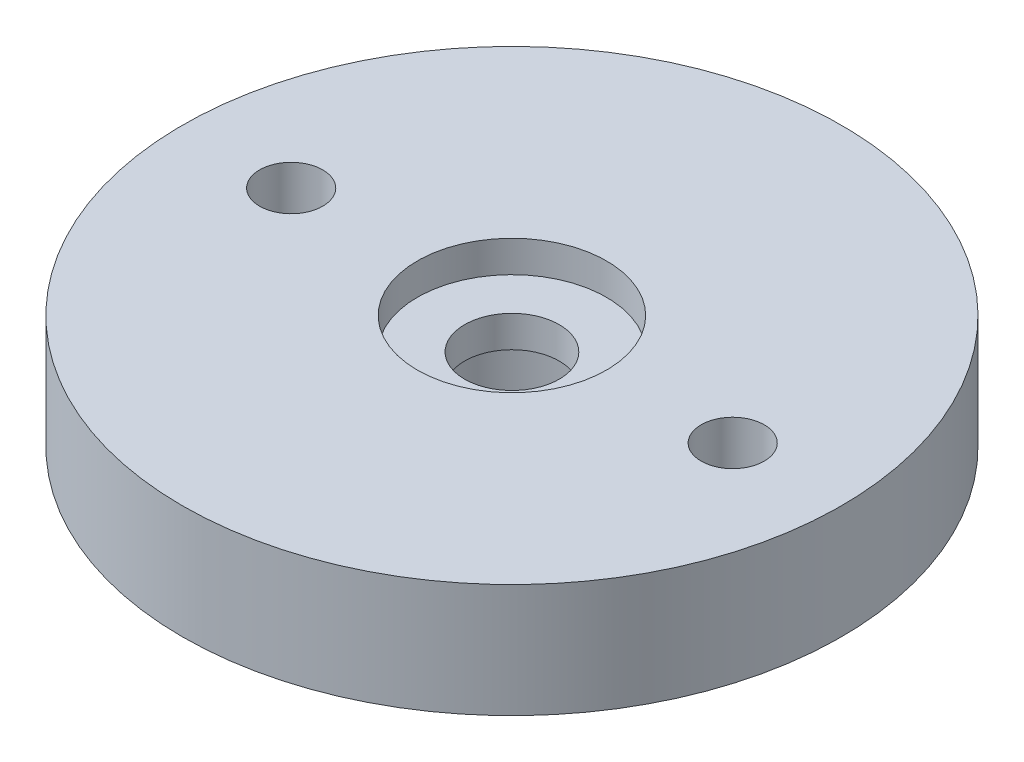
SolidWorks part; units mm, degrees
note: The reader was unsure of these and kept them because the rebuilt part matched: shared geometry of "Croquis1<3>".
ref_plane "Alzado" through (0, 0, 0) normal (0, 0, 1) x (1, 0, 0)
ref_plane "Planta" through (0, 0, 0) normal (0, 1, 0) x (1, 0, 0)
ref_plane "Vista lateral" through (0, 0, 0) normal (1, 0, 0) x (0, 0, -1)
sketch "Croquis1" plane through (0, 0, 0) normal (0, 1, 0) x (1, 0, 0)
  circle A0 centre (0, 0) radius 10.45
  circle A1 centre (0, 0) radius 4.25
  circle A2 centre (0, 0) radius 3
  dimension "D1" = 20.9
  dimension "D2" = 8.5
  dimension "D3" = 6
extrude "Saliente-Extruir1" add sketch "Croquis1" against normal blind 3.6 contours A0 A1 | A2
extrude "Saliente-Extruir2" add sketch "Croquis1<3>" against normal blind 6 contours A1 A2 | A2
sketch "Croquis1<3>" plane through (0, 0, 0) normal (0, 1, 0) x (1, 0, 0) same geometry as "Croquis1"
sketch "Croquis3" plane through (0, 0, 0) normal (0, 1, 0) x (1, 0, 0)
  line L0 (-10.45, 0) -> (10.45, 0) construction
  line L1 (0, 10.45) -> (0, -10.45) construction
  circle A0 centre (0, 0) radius 10.45 construction
  circle A1 centre (7, 0) radius 1
  circle A2 centre (-7, 0) radius 1
  dimension "D1" = 2
  dimension "D2" = 14
extrude "Cortar-Extruir1" cut sketch "Croquis3" against normal up to next
sketch "Croquis4" plane through (0, 0, 0) normal (0, 1, 0) x (1, 0, 0)
  circle A0 centre (0, 0) radius 3
  dimension "D1" = 6
extrude "Saliente-Extruir3" add sketch "Croquis4" against normal blind 1 from offset 1 offset against normal yes
sketch "Croquis5" plane through (0, -1, 0) normal (0, 1, 0) x (1, 0, 0)
  circle A0 centre (0, 0) radius 1.5
  dimension "D1" = 3
extrude "Cortar-Extruir2" cut sketch "Croquis5" against normal blind 1
